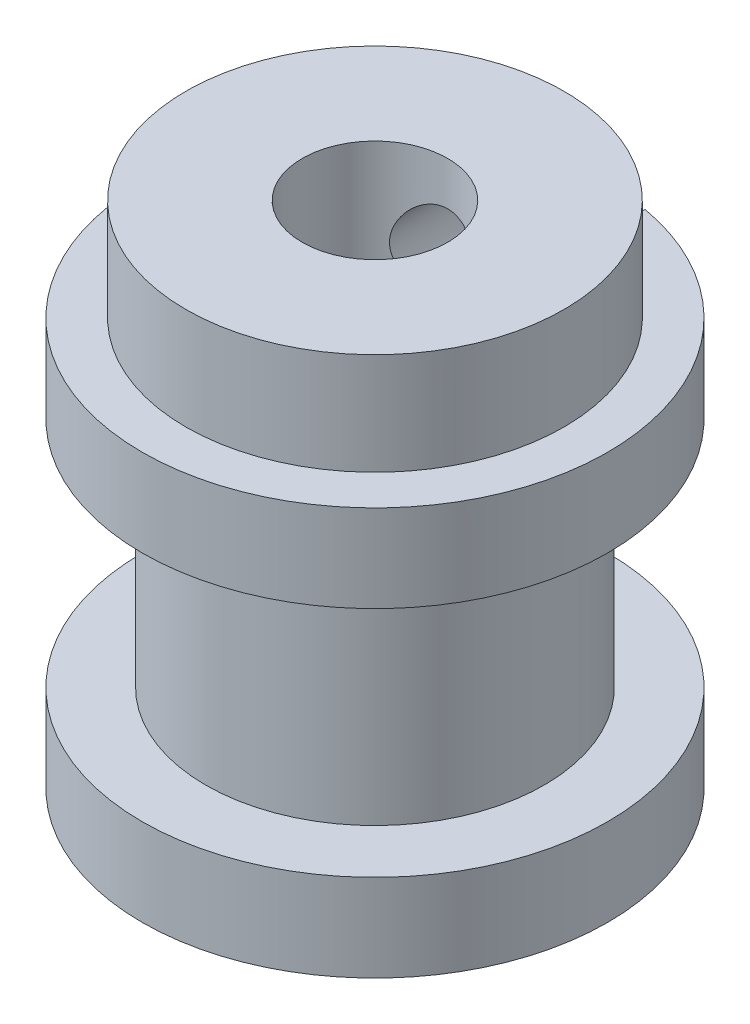
SolidWorks part; units mm, degrees
ref_plane "Plan de face" through (0, 0, 0) normal (0, 0, 1) x (1, 0, 0)
ref_plane "Plan de dessus" through (0, 0, 0) normal (0, 1, 0) x (1, 0, 0)
ref_plane "Plan de droite" through (0, 0, 0) normal (1, 0, 0) x (0, 0, -1)
sketch "Esquisse1" plane through (0, 0, 0) normal (0, 0, 1) x (1, 0, 0)
  line L0 (0, 5.9193) -> (0, -5.4162) construction
  line L1 (2.5, -7) -> (2.5, 10.5)
  line L2 (2.5, 10.5) -> (6.5, 10.5)
  line L3 (6.5, 10.5) -> (6.5, 7)
  line L4 (6.5, 7) -> (8, 7)
  line L5 (8, 7) -> (8, 4)
  line L6 (8, 4) -> (5.82, 4)
  line L7 (5.82, 4) -> (5.82, -4)
  line L8 (5.82, -4) -> (8, -4)
  line L9 (8, -4) -> (8, -7)
  line L10 (8, -7) -> (2.5, -7)
  line L11 (0, 0) -> (14.9645, 0) construction
  point P15 (7.5, -0.4676)
  dimension "D1" = 16
  dimension "D2" = 11.64
  dimension "D3" = 14
  dimension "D4" = 17.5
  dimension "D5" = 8
  dimension "D6" = 5
  dimension "D7" = 13
revolve "Révolution1" add sketch "Esquisse1" angle 360 about L0
sketch "Esquisse2" plane through (0, 0, 0) normal (0, 0, 1) x (1, 0, 0)
  line L0 (2.5, 10.5) -> (-2.5, 10.5) construction
  circle A0 centre (0, 7.5) radius 1.5
  point P4 (0, 0)
  dimension "D1" = 3
  dimension "D2" = 3
extrude "Enlèv. mat.-Extru.1" cut sketch "Esquisse2" against normal through all
